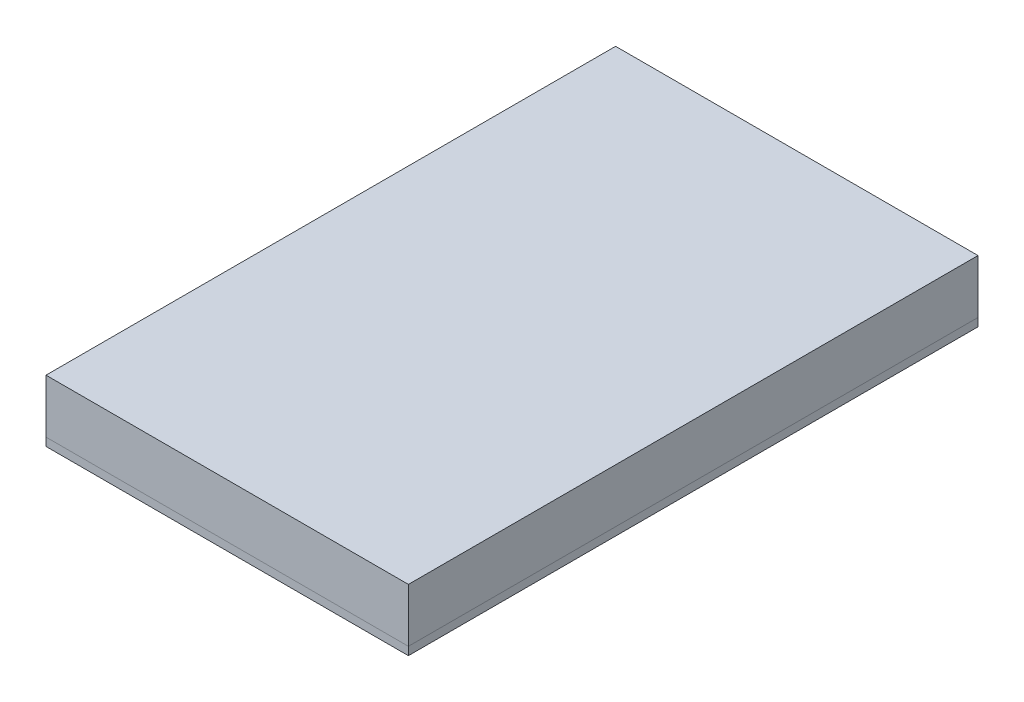
SolidWorks part; units mm, degrees
ref_plane "Front Plane" through (0, 0, 0) normal (0, 0, 1) x (1, 0, 0)
ref_plane "Top Plane" through (0, 0, 0) normal (0, 1, 0) x (1, 0, 0)
ref_plane "Right Plane" through (0, 0, 0) normal (1, 0, 0) x (0, 0, -1)
sketch "Sketch1" plane through (0, 0, 0) normal (0, 1, 0) x (1, 0, 0)
  line L0 (15.8, -28.05) -> (15.8, 28.05)
  line L1 (-17.3, -29.55) -> (17.3, -29.55) construction
  line L2 (-17.3, -29.55) -> (-17.3, 29.55) construction
  line L3 (-17.3, 29.55) -> (17.3, 29.55) construction
  line L4 (17.3, -29.55) -> (17.3, 29.55) construction
  line L5 (-17.3, -29.55) -> (17.3, 29.55) construction
  line L6 (-17.3, 29.55) -> (17.3, -29.55) construction
  line L7 (-22.3, 35.55) -> (22.3, 35.55)
  line L8 (-22.3, 35.55) -> (-22.3, -34.55)
  line L9 (-22.3, -34.55) -> (22.3, -34.55)
  line L10 (22.3, 35.55) -> (22.3, -34.55)
  line L11 (-15.8, 28.05) -> (15.8, 28.05)
  line L12 (-15.8, -28.05) -> (-15.8, 28.05)
  line L13 (-15.8, -28.05) -> (15.8, -28.05)
  line L15 (-6.8, 28.05) -> (6.8, 28.05)
  line L16 (-6.8, 28.05) -> (-6.8, 33.85)
  line L17 (-6.8, 33.85) -> (6.8, 33.85)
  line L18 (6.8, 28.05) -> (6.8, 33.85)
  point P0 (0, 0)
  point P18 (0, 33.85)
  dimension "D1" = 34.6
  dimension "D2" = 59.1
  dimension "D3" = 6
  dimension "D4" = 5
  dimension "D5" = 5
  dimension "D6" = 5
  dimension "D8" = 13.6
  dimension "D9" = 5.8
  dimension "D7" = 1.5
extrude "Boss-Extrude1" add sketch "Sketch1" along normal blind 5 contours L10 L7 L8 L9 L18 L11 L0 L13 L12 L16 L17 region at (0, 0, -34.7191)
sketch "Sketch2" plane through (0, 5, 0) normal (0, 1, 0) x (1, 0, 0)
  line L0 (-22.3, -34.55) -> (22.3, -34.55) construction
  line L1 (-22.3, 35.55) -> (22.3, 35.55)
  line L2 (-22.3, 35.55) -> (-22.3, -34.55)
  line L3 (-22.3, -34.55) -> (22.3, -34.55)
  line L4 (22.3, 35.55) -> (22.3, -34.55)
extrude "Boss-Extrude2" add sketch "Sketch2" against normal blind 1
sketch "Sketch3" plane through (0, 0, 0) normal (0, -1, 0) x (1, 0, 0)
  line L1 (-17.3, -29.55) -> (17.3, -29.55)
  line L2 (-17.3, -29.55) -> (-17.3, 29.55)
  line L3 (-17.3, 29.55) -> (17.3, 29.55)
  line L4 (17.3, -29.55) -> (17.3, 29.55)
  line L5 (-17.3, -29.55) -> (17.3, 29.55) construction
  line L6 (-17.3, 29.55) -> (17.3, -29.55) construction
  line L18 (-6.8, -29.55) -> (-6.8, -33.85)
  line L19 (-6.8, -28.05) -> (-6.8, -33.85) construction
  line L20 (-6.8, -33.85) -> (6.8, -33.85)
  line L21 (6.8, -33.85) -> (6.8, -29.55)
  line L22 (6.8, -28.05) -> (6.8, -33.85) construction
  line L24 (-22.3, 34.55) -> (22.3, 34.55)
  line L25 (-22.3, 34.55) -> (-22.3, -35.55)
  line L26 (-22.3, -35.55) -> (22.3, -35.55)
  line L27 (22.3, 34.55) -> (22.3, -35.55)
  point P0 (0, 0)
  line M13 (6.8, -28.05) -> (6.8, -33.85)
  line M14 (6.8, -33.85) -> (-6.8, -33.85)
  line M15 (-6.8, -33.85) -> (-6.8, -28.05)
  line M21 (22.3, -35.55) -> (22.3, 34.55)
  line M22 (22.3, 34.55) -> (-22.3, 34.55)
  line M23 (-22.3, 34.55) -> (-22.3, -35.55)
  line M24 (-22.3, -35.55) -> (22.3, -35.55)
  dimension "D1" = 34.6
  dimension "D2" = 59.1
extrude "Boss-Extrude3" add sketch "Sketch3" along normal blind 1.6 contours L4 L1 L2 L3 M24 M21 M22 M23 M13 M14 M15 region at (0, 0, 33.7191)
sketch "Sketch4" plane through (0, -1.6, 0) normal (0, -1, 0) x (1, 0, 0)
  line L1 (-22.3, 34.55) -> (22.3, 34.55)
  line L2 (-22.3, 34.55) -> (-22.3, -35.55)
  line L3 (-22.3, -35.55) -> (22.3, -35.55)
  line L4 (22.3, 34.55) -> (22.3, -35.55)
  line L5 (-1.8, 7.35) -> (1.8, 7.35)
  line L6 (-1.8, 7.35) -> (-1.8, 3.75)
  line L7 (-1.8, 3.75) -> (1.8, 3.75)
  line L8 (1.8, 7.35) -> (1.8, 3.75)
  line L9 (-1.8, -2.65) -> (1.8, -2.65)
  line L10 (-1.8, -2.65) -> (-1.8, -6.25)
  line L11 (-1.8, -6.25) -> (1.8, -6.25)
  line L12 (1.8, -2.65) -> (1.8, -6.25)
  line L13 (-1.8, -12.65) -> (1.8, -12.65)
  line L14 (-1.8, -12.65) -> (-1.8, -16.25)
  line L15 (-1.8, -16.25) -> (1.8, -16.25)
  line L16 (1.8, -12.65) -> (1.8, -16.25)
  point P18 (0, -16.25)
  point P19 (0, -35.55)
  point P20 (1.8, -5.1849)
  dimension "D1" = 3.6
  dimension "D2" = 10
  dimension "D3" = 10
  dimension "D4" = 19.3
extrude "Boss-Extrude4" add sketch "Sketch4" along normal blind 1 separate body
